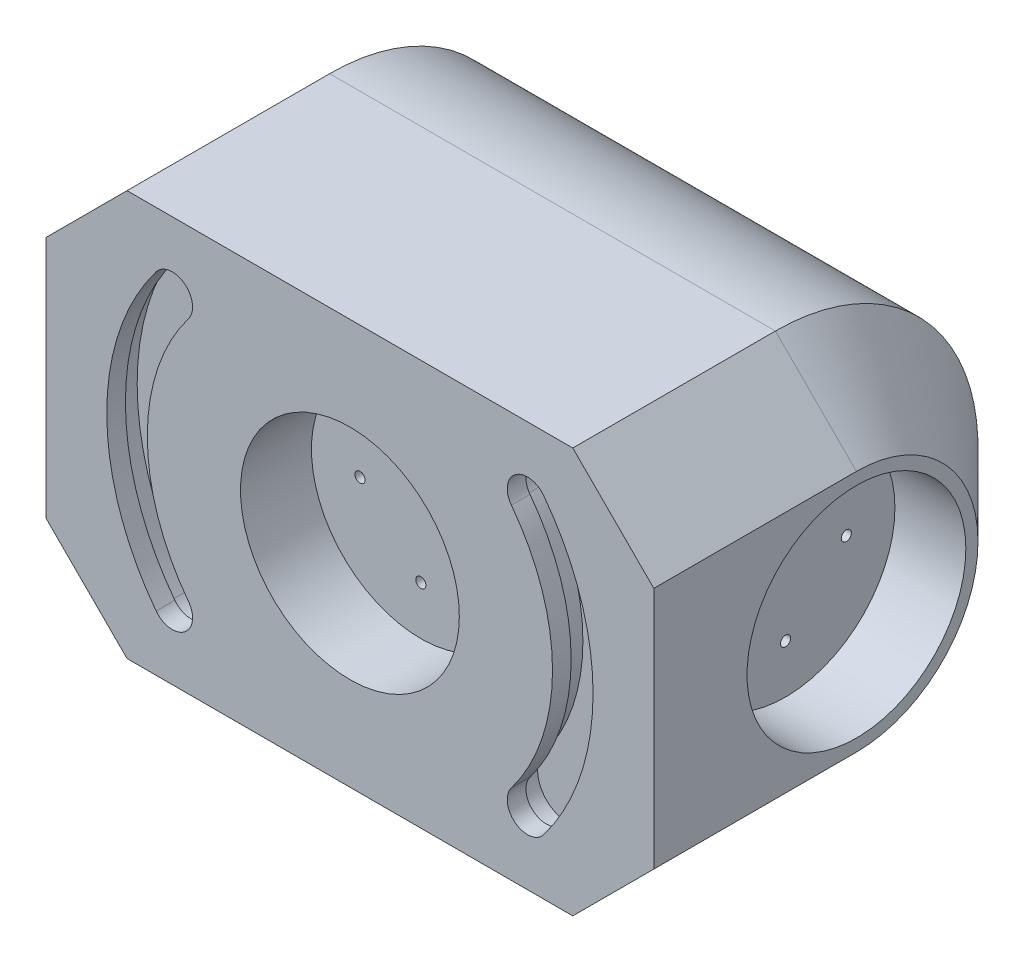
SolidWorks part; units mm, degrees
ref_plane "Front Plane" through (0, 0, 0) normal (0, 0, 1) x (1, 0, 0)
ref_plane "Top Plane" through (0, 0, 0) normal (0, 1, 0) x (1, 0, 0)
ref_plane "Right Plane" through (0, 0, 0) normal (1, 0, 0) x (0, 0, -1)
sketch "Sketch1" plane through (0, 0, 0) normal (0, 0, 1) x (1, 0, 0)
  line L1 (-150, -100) -> (150, -100)
  line L2 (-150, -100) -> (-150, 100)
  line L3 (-150, 100) -> (150, 100)
  line L4 (150, -100) -> (150, 100)
  line L5 (-150, -100) -> (150, 100) construction
  line L6 (-150, 100) -> (150, -100) construction
  point P0 (0, 0)
  dimension "D1" = 200
  dimension "D2" = 300
extrude "Boss-Extrude1" add sketch "Sketch1" against normal blind 200
sketch "Sketch2" plane through (150, 0, 0) normal (1, 0, 0) x (0, 0, -1)
  line L0 (100, 100) -> (200, 100)
  line L1 (200, 100) -> (200, -100)
  line L2 (200, -100) -> (100, -100)
  arc A0 (100, 100) -> (100, -100) centre (100, 0) cw
  line M6 (0, -100) -> (200, -100)
  line M7 (200, -100) -> (200, 100)
  line M8 (200, 100) -> (0, 100)
extrude "Cut-Extrude1" cut sketch "Sketch2" against normal through all contours A0 L1 M8 | A0 M7 M6 region at (150, -77.6632, -177.6632) region at (150, 77.6632, -177.6632)
sketch "Sketch3" plane through (150, 0, 0) normal (1, 0, 0) x (0, 0, -1)
  line L0 (0, 0) -> (200, 0) construction
  arc A0 (100, -100) -> (100, 100) centre (100, 0) ccw construction
  circle A1 centre (100, 0) radius 54
  dimension "D1" = 108
extrude "Cut-Extrude2" cut sketch "Sketch3" against normal blind 35
sketch "Sketch6" plane through (-150, 0, 0) normal (-1, 0, 0) x (0, 0, 1)
  line L0 (0, 100) -> (0, -100)
  line L1 (0, -100) -> (-100, -100)
  line L2 (0, 100) -> (-100, 100)
  arc A0 (-100, -100) -> (-100, 100) centre (-100, 0) cw
extrude "Cut-Extrude4" cut sketch "Sketch6" against normal blind 150
mirror "Mirror1" about plane through (0, 0, -100) normal (1, 0, 0) of bodies 106
sketch "Sketch7" plane through (0, 0, 0) normal (0, 0, 1) x (1, 0, 0)
  line L0 (0, 0) -> (0, 125) construction
  line L1 (0, 0) -> (-88.3883, 88.3883) construction
  line L2 (-88.3883, -88.3883) -> (95.4594, 95.4594) construction
  line L3 (0, 0) -> (-88.3883, -88.3883) construction
  line L4 (0, 0) -> (88.3883, -88.3883) construction
  arc A0 (-99.6157, 75.5097) -> (-99.6157, -75.5097) centre (0, 0) ccw
  arc A1 (-75.7079, 57.3874) -> (-75.7079, -57.3874) centre (0, 0) ccw
  arc A2 (-99.6157, 75.5097) -> (-75.7079, 57.3874) centre (-87.6618, 66.4486) cw
  arc A3 (-99.6157, -75.5097) -> (-75.7079, -57.3874) centre (-87.6618, -66.4486) ccw
  arc A4 (75.7079, 57.3874) -> (99.6157, 75.5097) centre (87.6618, 66.4486) cw
  arc A5 (75.7079, -57.3874) -> (99.6157, -75.5097) centre (87.6618, -66.4486) ccw
  arc A6 (99.6157, -75.5097) -> (99.6157, 75.5097) centre (0, 0) ccw
  arc A7 (75.7079, -57.3874) -> (75.7079, 57.3874) centre (0, 0) ccw
  dimension "D1" = 250
  dimension "D2" = 190
  dimension "D3" = 45
  dimension "D4" = 45
extrude "Cut-Extrude5" cut sketch "Sketch7" against normal blind 20
sketch "Sketch10" plane through (0, 0, 0) normal (0, 0, 1) x (1, 0, 0)
  arc A0 (-75.7079, 57.3874) -> (-75.7079, -57.3874) centre (0, 0) ccw
  arc A1 (-99.6157, 75.5097) -> (-99.6157, -75.5097) centre (0, 0) ccw
  arc A2 (-75.7079, 57.3874) -> (-99.6157, 75.5097) centre (-87.6618, 66.4486) ccw
  arc A3 (-99.6157, -75.5097) -> (-75.7079, -57.3874) centre (-87.6618, -66.4486) ccw
  arc A4 (75.7079, -57.3874) -> (99.6157, -75.5097) centre (87.6618, -66.4486) ccw
  arc A5 (99.6157, 75.5097) -> (75.7079, 57.3874) centre (87.6618, 66.4486) ccw
  arc A6 (75.7079, -57.3874) -> (75.7079, 57.3874) centre (0, 0) ccw
  arc A7 (99.6157, -75.5097) -> (99.6157, 75.5097) centre (0, 0) ccw
  arc A8 (-79.6925, 60.4078) -> (-79.6925, -60.4078) centre (0, 0) ccw
  arc A9 (-95.631, 72.4894) -> (-95.631, -72.4894) centre (0, 0) ccw
  arc A10 (-79.6925, 60.4078) -> (-95.631, 72.4894) centre (-87.6618, 66.4486) ccw
  arc A11 (-95.631, -72.4894) -> (-79.6925, -60.4078) centre (-87.6618, -66.4486) ccw
  arc A12 (79.6925, -60.4078) -> (95.631, -72.4894) centre (87.6618, -66.4486) ccw
  arc A13 (95.631, 72.4894) -> (79.6925, 60.4078) centre (87.6618, 66.4486) ccw
  arc A14 (95.631, -72.4894) -> (95.631, 72.4894) centre (0, 0) ccw
  arc A15 (79.6925, -60.4078) -> (79.6925, 60.4078) centre (0, 0) ccw
  dimension "D1" = 190
  dimension "D2" = 250
  dimension "D3" = 30
  dimension "D4" = 240
  dimension "D5" = 200
extrude "Boss-Extrude3" add sketch "Sketch10" against normal blind 9.2
sketch "Sketch11" plane through (0, 0, 0) normal (0, 0, 1) x (1, 0, 0)
  circle A0 centre (0, 0) radius 54
  dimension "D1" = 108
extrude "Cut-Extrude6" cut sketch "Sketch11" against normal blind 35
chamfer "Chamfer1" distance 40 angle 45 6 edges at (-150, 100, -50) (-150, 0, -200) (-150, -100, -50) (150, 100, -50) (150, 0, -200) (150, -100, -50)
sketch "Sketch13" plane through (-115, 0, 0) normal (-1, 0, 0) x (0, 0, 1)
  circle A0 centre (-100, 0) radius 54 construction
  circle A1 centre (-100, 0) radius 54
  circle A2 centre (-100, 0) radius 30 construction
  circle A3 centre (-100, 30) radius 2.5
  circle A4 centre (-130, 0) radius 2.5
  circle A5 centre (-100, -30) radius 2.5
  circle A6 centre (-70, 0) radius 2.5
  dimension "D1" = 60
  dimension "D2" = 5
  dimension "D3" = 5
  dimension "D4" = 5
  dimension "D5" = 5
extrude "Cut-Extrude7" cut sketch "Sketch13" against normal blind 10 contours A4 | A5 | A6 | A3
mirror "Mirror2" about plane through (0, 0, 0) normal (1, 0, 0) of "Cut-Extrude7"
sketch "Sketch14" plane through (0, 0, -35) normal (0, 0, 1) x (1, 0, 0)
  circle A0 centre (0, 0) radius 54 construction
  circle A1 centre (0, 0) radius 54
  circle A2 centre (0, 0) radius 30 construction
  circle A3 centre (0, 30) radius 2.5
  circle A4 centre (-30, 0) radius 2.5
  circle A5 centre (0, -30) radius 2.5
  circle A6 centre (30, 0) radius 2.5
  dimension "D1" = 60
  dimension "D2" = 5
  dimension "D3" = 5
  dimension "D4" = 5
  dimension "D5" = 5
extrude "Cut-Extrude8" cut sketch "Sketch14" against normal blind 10 contours A4 | A5 | A6 | A3
sketch "Sketch15" plane through (0, 0, 0) normal (1, 0, 0) x (0, 0, -1)
  line L0 (100, -100) -> (0, -100) construction
  line L1 (0, 100) -> (100, 100) construction
  line L2 (100, -100) -> (0, -100)
  line L3 (0, 100) -> (100, 100)
  line L4 (35, 54) -> (35, 32.5)
  line L5 (35, 27.5) -> (35, -27.5)
  line L6 (35, -32.5) -> (35, -54)
  line L7 (35, -32.5) -> (35, -54)
  line L8 (35, 27.5) -> (35, -27.5)
  line L9 (35, 54) -> (35, 32.5)
  line L10 (100, 60) -> (100, 100) construction
  line L11 (100, -60) -> (100, -100) construction
  line L12 (100, -90) -> (45, -90)
  line L13 (45, -90) -> (45, 90)
  line L14 (45, 90) -> (100, 90)
  line L15 (45, 32.5) -> (45, 27.5)
  line L16 (45, 32.5) -> (45, 27.5)
  arc A0 (100, -100) -> (100, 100) centre (100, 0) ccw construction
  arc A1 (100, -100) -> (100, 100) centre (100, 0) ccw
  arc A2 (100, 90) -> (100, -90) centre (100, 0) cw
  dimension "D1" = 10
extrude "Cut-Extrude9" cut sketch "Sketch15" against normal mid plane 210 contours A2 L14 L13 L12 region at (0, 0, -109.4482)
sketch "Sketch16" plane through (0, -100, 0) normal (0, -1, 0) x (1, 0, 0)
  line L0 (54, -35) -> (-54, -35) construction
  line L1 (54, -35) -> (-54, -35)
  line L2 (0, -35) -> (0, -65) construction
  line L3 (-90, -45) -> (90, -45)
  line L4 (-90, -95) -> (90, -95)
  line L5 (-90, -95) -> (-90, -35)
  line L6 (-90, -35) -> (90, -35)
  line L7 (90, -95) -> (90, -35)
  line L8 (-90, -95) -> (90, -35) construction
  line L9 (-90, -35) -> (90, -95) construction
  dimension "D1" = 60
  dimension "D2" = 180
  dimension "D3" = 10
extrude "Cut-Extrude10" cut sketch "Sketch16" against normal blind 15 contours L4 L7 L3 L5 region at (0, -100, -70)
sketch "Sketch17" plane through (0, -100, 0) normal (0, -1, 0) x (1, 0, 0)
  line L0 (90, -95) -> (90, -45) construction
  line L1 (-90, -95) -> (-90, -45) construction
  line L2 (90, -95) -> (90, -45)
  line L3 (-90, -95) -> (-90, -45)
  line L4 (110, 0) -> (-110, 0)
  line L5 (-110, 0) -> (-110, -100)
  line L6 (-110, -100) -> (110, -100)
  line L7 (110, -100) -> (110, 0)
  line L8 (110, 0) -> (-110, 0)
  line L9 (-110, 0) -> (-110, -100)
  line L10 (-110, -100) -> (110, -100)
  line L11 (110, -100) -> (110, 0)
  line L12 (-95, -100) -> (-95, 0) construction
  line L13 (95, -100) -> (95, 0) construction
  line L14 (-90, -45) -> (90, -45) construction
  line L16 (90, -45) -> (100, -45)
  line L17 (90, -45) -> (90, -95)
  line L18 (90, -95) -> (100, -95)
  line L19 (100, -45) -> (100, -95)
  line L20 (90, -45) -> (100, -95) construction
  line L21 (90, -95) -> (100, -45) construction
  line L22 (-90, -45) -> (-100, -45)
  line L23 (-90, -45) -> (-90, -95)
  line L24 (-90, -95) -> (-100, -95)
  line L25 (-100, -45) -> (-100, -95)
  line L26 (-90, -45) -> (-100, -95) construction
  line L27 (-90, -95) -> (-100, -45) construction
  circle A0 centre (-95, -50) radius 1.5
  circle A1 centre (95, -50) radius 1.5
  circle A2 centre (-95, -60) radius 1.5
  circle A3 centre (95, -60) radius 1.5
  circle A4 centre (-95, -70) radius 1.5
  circle A5 centre (95, -70) radius 1.5
  circle A6 centre (-95, -80) radius 1.5
  circle A7 centre (95, -80) radius 1.5
  circle A8 centre (-95, -90) radius 1.5
  circle A9 centre (95, -90) radius 1.5
  point P21 (95, -70)
  point P25 (-95, -70)
  dimension "D4" = 3
  dimension "D5" = 3
  dimension "D2" = 5
  dimension "D3" = 5
  dimension "D6" = 5
  dimension "D7" = 5
  dimension "D8" = 50
  dimension "D9" = 10
  dimension "D10" = 50
  dimension "D11" = 10
  dimension "D13" = 5
  dimension "D1" = 0
  dimension "D12" = 5
extrude "Cut-Extrude11" cut sketch "Sketch17" against normal blind 5 contours L22 L25 L24 L23 | L16 L19 L18 L17
extrude "Cut-Extrude12" cut sketch "Sketch17<3>" against normal blind 10 contours A0 | A2 | A4 | A6 | A8 | A1 | A3 | A5 | A7 | A9
sketch "Sketch17<3>" plane through (0, -100, 0) normal (0, -1, 0) x (1, 0, 0) same geometry as "Sketch17"
